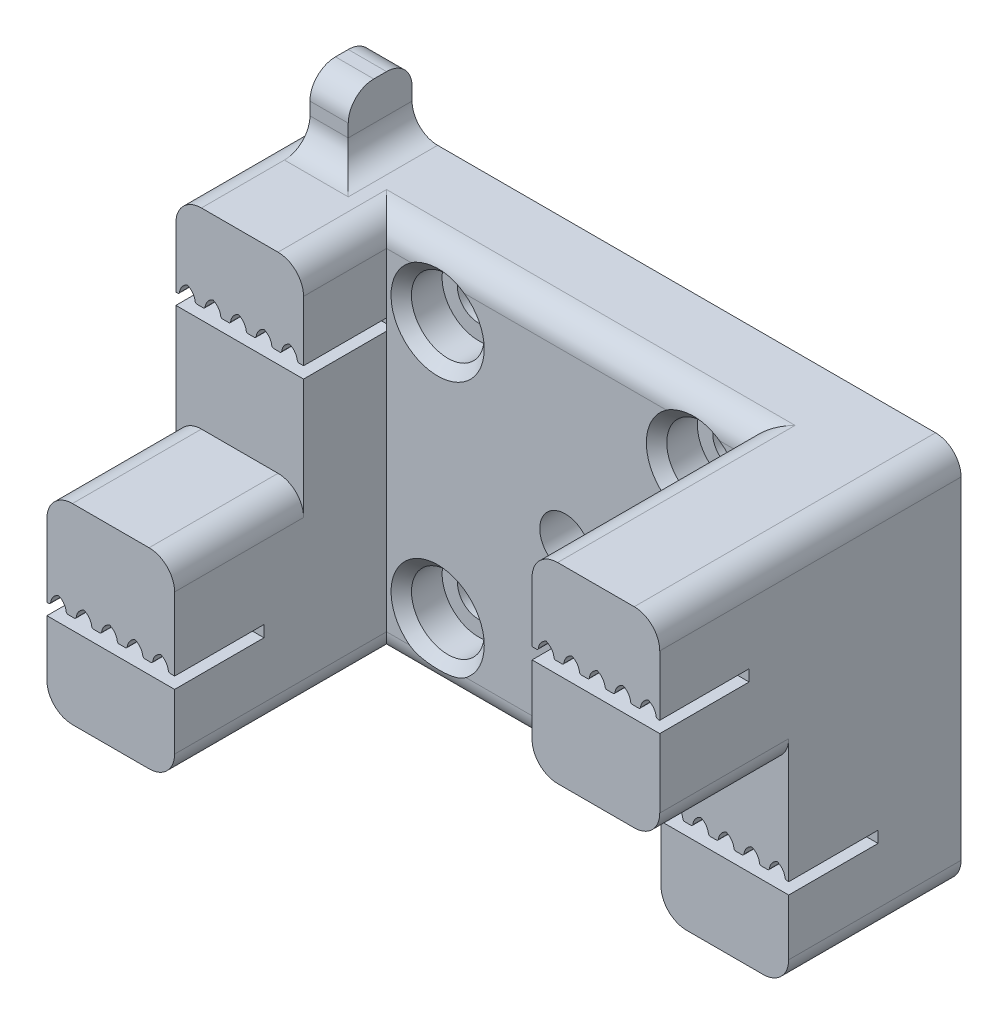
SolidWorks part; units mm, degrees
note: The reader was unsure of these and kept them because the rebuilt part matched: shared geometry of "Sketch2<3>".
ref_plane "Front Plane" through (0, 0, 0) normal (0, 0, 1) x (1, 0, 0)
ref_plane "Top Plane" through (0, 0, 0) normal (0, 1, 0) x (1, 0, 0)
ref_plane "Right Plane" through (0, 0, 0) normal (1, 0, 0) x (0, 0, -1)
sketch "Sketch1" plane through (0, 0, 0) normal (0, 0, 1) x (1, 0, 0)
  line L1 (-10, -10) -> (10, -10) construction
  line L2 (-10, -10) -> (-10, 10) construction
  line L3 (-10, 10) -> (10, 10) construction
  line L4 (10, -10) -> (10, 10) construction
  line L5 (-10, -10) -> (10, 10) construction
  line L6 (-10, 10) -> (10, -10) construction
  line L7 (-24, -15) -> (24, -15)
  line L8 (-24, -15) -> (-24, 15)
  line L9 (-24, 15) -> (24, 15)
  line L10 (24, -15) -> (24, 15)
  line L11 (-24, -15) -> (24, 15) construction
  line L12 (-24, 15) -> (24, -15) construction
  circle A0 centre (-10, 10) radius 1.65
  circle A1 centre (10, 10) radius 1.65
  circle A2 centre (10, -10) radius 1.65
  circle A3 centre (-9.9952, -10.0965) radius 1.65
  circle A4 centre (0, 0) radius 2
  point P0 (0, 0)
  dimension "D2" = 3.3
  dimension "D3" = 4
  dimension "D1" = 20
  dimension "D4" = 30
  dimension "D5" = 48
extrude "Boss-Extrude1" add sketch "Sketch1" along normal blind 7
sketch "Sketch2" plane through (0, 0, 7) normal (0, 0, 1) x (1, 0, 0)
  line L1 (-24, 15) -> (-14, 15)
  line L2 (-24, 15) -> (-24, -15)
  line L3 (-24, -15) -> (-14, -15)
  line L4 (-14, 15) -> (-14, -15)
  line L5 (-24, -15) -> (24, -15) construction
  line L7 (24, 15) -> (14, 15)
  line L8 (24, 15) -> (24, -15)
  line L9 (24, -15) -> (14, -15)
  line L10 (14, 15) -> (14, -15)
  line L11 (-14, -15) -> (-24, -15)
  line L12 (-14, -15) -> (-14, 0)
  line L13 (-14, 0) -> (-24, 0)
  line L14 (-24, -15) -> (-24, 0)
  line L15 (14, -15) -> (24, -15)
  line L16 (14, -15) -> (14, 0)
  line L17 (14, 0) -> (24, 0)
  line L18 (24, -15) -> (24, 0)
  line M1 (24, -15) -> (24, 15)
  line M2 (24, 15) -> (-24, 15)
  line M3 (-24, 15) -> (-24, -15)
  line M4 (-24, -15) -> (24, -15)
  dimension "D1" = 30
  dimension "D2" = 10
  dimension "D3" = 30
  dimension "D4" = 10
  dimension "D5" = 15
  dimension "D6" = 10
  dimension "D7" = 15
  dimension "D8" = 10
extrude "Boss-Extrude2" add sketch "Sketch2" along normal blind 16.6 contours L10 L17 L8 M2 | L4 L13 L2 M4
extrude "Boss-Extrude3" add sketch "Sketch2<3>" along normal blind 6.5 contours L17 L10 M4 M1 | L13 L4 M2 M3
sketch "Sketch2<3>" plane through (0, 0, 7) normal (0, 0, 1) x (1, 0, 0) same geometry as "Sketch2"
sketch "Sketch4" plane through (0, 0, 7) normal (0, 0, 1) x (1, 0, 0)
  circle A0 centre (-10, 10) radius 2.85
  circle A1 centre (10, 10) radius 2.85
  circle A2 centre (10, -10) radius 2.85
  circle A3 centre (-9.9952, -10.0965) radius 2.85
  dimension "D1" = 5.7
extrude "Cut-Extrude1" cut sketch "Sketch4" against normal blind 3.2
sketch "Sketch5" plane through (0, 0, 0) normal (0, 0, -1) x (-1, 0, 0)
  circle A0 centre (0, 0) radius 3.5
  dimension "D1" = 7
extrude "Cut-Extrude2" cut sketch "Sketch5" against normal blind 3
chamfer "Chamfer1" distance 0.8 angle 45 5 edges at (-3.5, 0, 0) (-7.15, 10, 7) (12.85, 10, 7) (-7.1452, -10.0965, 7) (12.85, -10, 7)
sketch "Sketch6" plane through (0, 0, 13.5) normal (0, 0, 1) x (1, 0, 0)
  line L7 (-16.343, 8.2928) -> (-15.8615, 8.2928)
  line L9 (-18.343, 8.2928) -> (-17.8615, 8.2928)
  line L10 (-20.343, 8.2928) -> (-19.8615, 8.2928)
  line L11 (-22.343, 8.2928) -> (-21.8615, 8.2928)
  line L12 (-23.8615, 8.2928) -> (-23.9973, 8.2928)
  line L14 (-23.9973, 8.2928) -> (-24, 8.2928)
  line L18 (-14.343, 8.2928) -> (-14, 8.2928)
  line L20 (-24.343, 8.2928) -> (-23.8615, 8.2928) [skipped]
  line L21 (-14.343, 8.2928) -> (-13.8615, 8.2928) [skipped]
  line L23 (-14, 6.5745) -> (-14, 8.2928)
  line L28 (-24, 8.2928) -> (-24, 7.3928)
  line L29 (-24, 7.3928) -> (-14, 7.3928)
  line L30 (-14, 8.2928) -> (-14, 7.3928)
  arc A13 (-17.1023, 9.2174) -> (-17.7128, 8.4232) centre (-16.7213, 8.2928) ccw
  arc A14 (-16.4917, 8.4232) -> (-17.1023, 9.2174) centre (-17.4832, 8.2928) ccw
  arc A15 (-16.4917, 8.4232) -> (-16.343, 8.2928) centre (-16.343, 8.4428) ccw
  arc A16 (-15.8615, 8.2928) -> (-15.7128, 8.4232) centre (-15.8615, 8.4428) ccw
  arc A19 (-19.1023, 9.2174) -> (-19.7128, 8.4232) centre (-18.7213, 8.2928) ccw
  arc A20 (-18.4917, 8.4232) -> (-19.1023, 9.2174) centre (-19.4832, 8.2928) ccw
  arc A21 (-18.4917, 8.4232) -> (-18.343, 8.2928) centre (-18.343, 8.4428) ccw
  arc A22 (-17.8615, 8.2928) -> (-17.7128, 8.4232) centre (-17.8615, 8.4428) ccw
  arc A23 (-21.1023, 9.2174) -> (-21.7128, 8.4232) centre (-20.7213, 8.2928) ccw
  arc A24 (-20.4917, 8.4232) -> (-21.1023, 9.2174) centre (-21.4832, 8.2928) ccw
  arc A25 (-20.4917, 8.4232) -> (-20.343, 8.2928) centre (-20.343, 8.4428) ccw
  arc A26 (-19.8615, 8.2928) -> (-19.7128, 8.4232) centre (-19.8615, 8.4428) ccw
  arc A27 (-23.1023, 9.2174) -> (-23.7128, 8.4232) centre (-22.7213, 8.2928) ccw
  arc A28 (-22.4917, 8.4232) -> (-23.1023, 9.2174) centre (-23.4832, 8.2928) ccw
  arc A29 (-22.4917, 8.4232) -> (-22.343, 8.2928) centre (-22.343, 8.4428) ccw
  arc A30 (-21.8615, 8.2928) -> (-21.7128, 8.4232) centre (-21.8615, 8.4428) ccw
  arc A34 (-23.8615, 8.2928) -> (-23.7128, 8.4232) centre (-23.8615, 8.4428) ccw
  arc A35 (-15.1023, 9.2174) -> (-15.7128, 8.4232) centre (-14.7213, 8.2928) ccw
  arc A36 (-14.4917, 8.4232) -> (-15.1023, 9.2174) centre (-15.4832, 8.2928) ccw
  arc A37 (-14.4917, 8.4232) -> (-14.343, 8.2928) centre (-14.343, 8.4428) ccw
  arc A39 (-24.4917, 8.4232) -> (-24.343, 8.2928) centre (-24.343, 8.4428) ccw [skipped]
  arc A40 (-24.4917, 8.4232) -> (-25.1023, 9.2174) centre (-25.4832, 8.2928) ccw [skipped]
  arc A41 (-25.1023, 9.2174) -> (-25.7128, 8.4232) centre (-24.7213, 8.2928) ccw [skipped]
  arc A42 (-13.8615, 8.2928) -> (-13.7128, 8.4232) centre (-13.8615, 8.4428) ccw [skipped]
  dimension "D2" = 2
  dimension "D3" = 10
  dimension "D4" = 0.9
  dimension "D1" = 5
extrude "Cut-Extrude3" cut sketch "Sketch6" against normal blind 7 and the other way blind 100 contours L18 A37 A36 A35 A16 L7 A15 A14 A13 A22 L9 A21 A20 A19 A26 L10 A25 A24 A23 A30 L11 A29 A28 A27 A34 L12 L14 L28 L29 L30
mirror "Mirror3" about plane through (0, 0, 0) normal (1, 0, 0) of "Cut-Extrude3"
pattern_linear "LPattern1" count 2 spacing 16 along (0, -1, 0) of "Mirror3", "Cut-Extrude3"
sketch "Sketch7" plane through (0, 0, 6.5) normal (0, 0, 1) x (1, 0, 0)
  line L0 (-14, 15) -> (-14, 8.2928) construction
  line L1 (-24, -8.6072) -> (-14, -8.6072)
  line L2 (-24, -8.6072) -> (-24, -6.1072)
  line L3 (-24, -6.1072) -> (-14, -6.1072)
  line L4 (-14, -8.6072) -> (-14, -6.1072)
  line L6 (14, 7.3928) -> (24, 7.3928)
  line L7 (14, 7.3928) -> (14, 9.8928)
  line L8 (14, 9.8928) -> (24, 9.8928)
  line L9 (24, 7.3928) -> (24, 9.8928)
  line L14 (14, 8.2928) -> (14, 7.3928)
  line L15 (14, 7.3928) -> (24, 7.3928)
  line L16 (24, 7.3928) -> (24, 8.2928)
  line L17 (24, 8.2928) -> (23.8615, 8.2928)
  line L18 (22.343, 8.2928) -> (21.8615, 8.2928)
  line L19 (20.343, 8.2928) -> (19.8615, 8.2928)
  line L20 (18.343, 8.2928) -> (17.8615, 8.2928)
  line L21 (16.343, 8.2928) -> (15.8615, 8.2928)
  line L22 (14.343, 8.2928) -> (14, 8.2928)
  line L24 (14, 7.3928) -> (24, 7.3928)
  line L25 (24, 7.3928) -> (24, 8.2928)
  line L26 (24, 8.2928) -> (23.8615, 8.2928)
  line L27 (22.343, 8.2928) -> (21.8615, 8.2928)
  line L28 (20.343, 8.2928) -> (19.8615, 8.2928)
  line L29 (18.343, 8.2928) -> (17.8615, 8.2928)
  line L30 (16.343, 8.2928) -> (15.8615, 8.2928)
  line L31 (14.343, 8.2928) -> (14, 8.2928)
  line L32 (23.8615, 8.2928) -> (24, 8.2928)
  line L33 (24, 8.2928) -> (24, 15)
  line L34 (24, 15) -> (14, 15)
  line L35 (14, 15) -> (14, 8.2928)
  line L36 (14, 8.2928) -> (14.343, 8.2928)
  line L37 (15.8615, 8.2928) -> (16.343, 8.2928)
  line L38 (17.8615, 8.2928) -> (18.343, 8.2928)
  line L39 (19.8615, 8.2928) -> (20.343, 8.2928)
  line L40 (21.8615, 8.2928) -> (22.343, 8.2928)
  line L41 (23.8615, 8.2928) -> (24, 8.2928)
  line L42 (24, 8.2928) -> (24, 15)
  line L43 (24, 15) -> (14, 15)
  line L44 (14, 15) -> (14, 8.2928)
  line L45 (14, 8.2928) -> (14.343, 8.2928)
  line L46 (15.8615, 8.2928) -> (16.343, 8.2928)
  line L47 (17.8615, 8.2928) -> (18.343, 8.2928)
  line L48 (19.8615, 8.2928) -> (20.343, 8.2928)
  line L49 (21.8615, 8.2928) -> (22.343, 8.2928)
  line L54 (14, 8.2928) -> (14, 7.3928)
  arc A21 (23.7128, 8.4232) -> (23.8615, 8.2928) centre (23.8615, 8.4428) ccw
  arc A22 (23.7128, 8.4232) -> (23.1023, 9.2174) centre (22.7213, 8.2928) ccw
  arc A23 (23.1023, 9.2174) -> (22.4917, 8.4232) centre (23.4832, 8.2928) ccw
  arc A24 (22.343, 8.2928) -> (22.4917, 8.4232) centre (22.343, 8.4428) ccw
  arc A25 (21.7128, 8.4232) -> (21.8615, 8.2928) centre (21.8615, 8.4428) ccw
  arc A26 (21.7128, 8.4232) -> (21.1023, 9.2174) centre (20.7213, 8.2928) ccw
  arc A27 (21.1023, 9.2174) -> (20.4917, 8.4232) centre (21.4832, 8.2928) ccw
  arc A28 (20.343, 8.2928) -> (20.4917, 8.4232) centre (20.343, 8.4428) ccw
  arc A29 (19.7128, 8.4232) -> (19.8615, 8.2928) centre (19.8615, 8.4428) ccw
  arc A30 (19.7128, 8.4232) -> (19.1023, 9.2174) centre (18.7213, 8.2928) ccw
  arc A31 (19.1023, 9.2174) -> (18.4917, 8.4232) centre (19.4832, 8.2928) ccw
  arc A32 (18.343, 8.2928) -> (18.4917, 8.4232) centre (18.343, 8.4428) ccw
  arc A33 (17.7128, 8.4232) -> (17.8615, 8.2928) centre (17.8615, 8.4428) ccw
  arc A34 (17.7128, 8.4232) -> (17.1023, 9.2174) centre (16.7213, 8.2928) ccw
  arc A35 (17.1023, 9.2174) -> (16.4917, 8.4232) centre (17.4832, 8.2928) ccw
  arc A36 (16.343, 8.2928) -> (16.4917, 8.4232) centre (16.343, 8.4428) ccw
  arc A37 (15.7128, 8.4232) -> (15.8615, 8.2928) centre (15.8615, 8.4428) ccw
  arc A38 (15.7128, 8.4232) -> (15.1023, 9.2174) centre (14.7213, 8.2928) ccw
  arc A39 (15.1023, 9.2174) -> (14.4917, 8.4232) centre (15.4832, 8.2928) ccw
  arc A40 (14.343, 8.2928) -> (14.4917, 8.4232) centre (14.343, 8.4428) ccw
  arc A41 (23.7128, 8.4232) -> (23.8615, 8.2928) centre (23.8615, 8.4428) ccw
  arc A42 (23.7128, 8.4232) -> (23.1023, 9.2174) centre (22.7213, 8.2928) ccw
  arc A43 (23.1023, 9.2174) -> (22.4917, 8.4232) centre (23.4832, 8.2928) ccw
  arc A44 (22.343, 8.2928) -> (22.4917, 8.4232) centre (22.343, 8.4428) ccw
  arc A45 (21.7128, 8.4232) -> (21.8615, 8.2928) centre (21.8615, 8.4428) ccw
  arc A46 (21.7128, 8.4232) -> (21.1023, 9.2174) centre (20.7213, 8.2928) ccw
  arc A47 (21.1023, 9.2174) -> (20.4917, 8.4232) centre (21.4832, 8.2928) ccw
  arc A48 (20.343, 8.2928) -> (20.4917, 8.4232) centre (20.343, 8.4428) ccw
  arc A49 (19.7128, 8.4232) -> (19.8615, 8.2928) centre (19.8615, 8.4428) ccw
  arc A50 (19.7128, 8.4232) -> (19.1023, 9.2174) centre (18.7213, 8.2928) ccw
  arc A51 (19.1023, 9.2174) -> (18.4917, 8.4232) centre (19.4832, 8.2928) ccw
  arc A52 (18.343, 8.2928) -> (18.4917, 8.4232) centre (18.343, 8.4428) ccw
  arc A53 (17.7128, 8.4232) -> (17.8615, 8.2928) centre (17.8615, 8.4428) ccw
  arc A54 (17.7128, 8.4232) -> (17.1023, 9.2174) centre (16.7213, 8.2928) ccw
  arc A55 (17.1023, 9.2174) -> (16.4917, 8.4232) centre (17.4832, 8.2928) ccw
  arc A56 (16.343, 8.2928) -> (16.4917, 8.4232) centre (16.343, 8.4428) ccw
  arc A57 (15.7128, 8.4232) -> (15.8615, 8.2928) centre (15.8615, 8.4428) ccw
  arc A58 (15.7128, 8.4232) -> (15.1023, 9.2174) centre (14.7213, 8.2928) ccw
  arc A59 (15.1023, 9.2174) -> (14.4917, 8.4232) centre (15.4832, 8.2928) ccw
  arc A60 (14.343, 8.2928) -> (14.4917, 8.4232) centre (14.343, 8.4428) ccw
  arc A61 (14.343, 8.2928) -> (14.4917, 8.4232) centre (14.343, 8.4428) ccw
  arc A62 (15.1023, 9.2174) -> (14.4917, 8.4232) centre (15.4832, 8.2928) ccw
  arc A63 (15.7128, 8.4232) -> (15.1023, 9.2174) centre (14.7213, 8.2928) ccw
  arc A64 (15.7128, 8.4232) -> (15.8615, 8.2928) centre (15.8615, 8.4428) ccw
  arc A65 (16.343, 8.2928) -> (16.4917, 8.4232) centre (16.343, 8.4428) ccw
  arc A66 (17.1023, 9.2174) -> (16.4917, 8.4232) centre (17.4832, 8.2928) ccw
  arc A67 (17.7128, 8.4232) -> (17.1023, 9.2174) centre (16.7213, 8.2928) ccw
  arc A68 (17.7128, 8.4232) -> (17.8615, 8.2928) centre (17.8615, 8.4428) ccw
  arc A69 (18.343, 8.2928) -> (18.4917, 8.4232) centre (18.343, 8.4428) ccw
  arc A70 (19.1023, 9.2174) -> (18.4917, 8.4232) centre (19.4832, 8.2928) ccw
  arc A71 (19.7128, 8.4232) -> (19.1023, 9.2174) centre (18.7213, 8.2928) ccw
  arc A72 (19.7128, 8.4232) -> (19.8615, 8.2928) centre (19.8615, 8.4428) ccw
  arc A73 (20.343, 8.2928) -> (20.4917, 8.4232) centre (20.343, 8.4428) ccw
  arc A74 (21.1023, 9.2174) -> (20.4917, 8.4232) centre (21.4832, 8.2928) ccw
  arc A75 (21.7128, 8.4232) -> (21.1023, 9.2174) centre (20.7213, 8.2928) ccw
  arc A76 (21.7128, 8.4232) -> (21.8615, 8.2928) centre (21.8615, 8.4428) ccw
  arc A77 (22.343, 8.2928) -> (22.4917, 8.4232) centre (22.343, 8.4428) ccw
  arc A78 (23.1023, 9.2174) -> (22.4917, 8.4232) centre (23.4832, 8.2928) ccw
  arc A79 (23.7128, 8.4232) -> (23.1023, 9.2174) centre (22.7213, 8.2928) ccw
  arc A80 (23.7128, 8.4232) -> (23.8615, 8.2928) centre (23.8615, 8.4428) ccw
  arc A81 (14.343, 8.2928) -> (14.4917, 8.4232) centre (14.343, 8.4428) ccw
  arc A82 (15.1023, 9.2174) -> (14.4917, 8.4232) centre (15.4832, 8.2928) ccw
  arc A83 (15.7128, 8.4232) -> (15.1023, 9.2174) centre (14.7213, 8.2928) ccw
  arc A84 (15.7128, 8.4232) -> (15.8615, 8.2928) centre (15.8615, 8.4428) ccw
  arc A85 (16.343, 8.2928) -> (16.4917, 8.4232) centre (16.343, 8.4428) ccw
  arc A86 (17.1023, 9.2174) -> (16.4917, 8.4232) centre (17.4832, 8.2928) ccw
  arc A87 (17.7128, 8.4232) -> (17.1023, 9.2174) centre (16.7213, 8.2928) ccw
  arc A88 (17.7128, 8.4232) -> (17.8615, 8.2928) centre (17.8615, 8.4428) ccw
  arc A89 (18.343, 8.2928) -> (18.4917, 8.4232) centre (18.343, 8.4428) ccw
  arc A90 (19.1023, 9.2174) -> (18.4917, 8.4232) centre (19.4832, 8.2928) ccw
  arc A91 (19.7128, 8.4232) -> (19.1023, 9.2174) centre (18.7213, 8.2928) ccw
  arc A92 (19.7128, 8.4232) -> (19.8615, 8.2928) centre (19.8615, 8.4428) ccw
  arc A93 (20.343, 8.2928) -> (20.4917, 8.4232) centre (20.343, 8.4428) ccw
  arc A94 (21.1023, 9.2174) -> (20.4917, 8.4232) centre (21.4832, 8.2928) ccw
  arc A95 (21.7128, 8.4232) -> (21.1023, 9.2174) centre (20.7213, 8.2928) ccw
  arc A96 (21.7128, 8.4232) -> (21.8615, 8.2928) centre (21.8615, 8.4428) ccw
  arc A97 (22.343, 8.2928) -> (22.4917, 8.4232) centre (22.343, 8.4428) ccw
  arc A98 (23.1023, 9.2174) -> (22.4917, 8.4232) centre (23.4832, 8.2928) ccw
  arc A99 (23.7128, 8.4232) -> (23.1023, 9.2174) centre (22.7213, 8.2928) ccw
  arc A100 (23.7128, 8.4232) -> (23.8615, 8.2928) centre (23.8615, 8.4428) ccw
  dimension "D1" = 2.5
  dimension "D2" = 0
  dimension "D3" = 0
  dimension "D4" = 2.5
  dimension "D5" = 10
extrude "Boss-Extrude4" add sketch "Sketch7" along normal blind 10.1
fillet "Fillet1" radius 2 14 edges at (0, 15, 7) (0, -15, 7) (14, 15, 15.3) (14, 0, 18.55) (24, 0, 18.55) (-14, -15, 15.3) (-14, 0, 18.55) (-24, 0, 18.55) (14, -15, 10.25) (-14, 15, 10.25) (24, -15, 6.75) (-24, -15, 11.8) (-24, 15, 6.75) (24, 15, 11.8)
sketch "Sketch10" plane through (0, 15, 0) normal (0, 1, 0) x (1, 0, 0)
  line L0 (22, 0) -> (-22, 0) construction
  line L1 (-22, 0) -> (-19, 0)
  line L2 (-22, 0) -> (-22, -5)
  line L3 (-22, -5) -> (-19, -5)
  line L4 (-19, 0) -> (-19, -5)
  line L5 (-16, -5) -> (16, -5) construction
  dimension "D1" = 3
  dimension "D2" = 19
extrude "Boss-Extrude7" add sketch "Sketch10" along normal blind 5
fillet "Fillet3" radius 2 4 edges at (-20.5, 15, 5) (-20.5, 20, 0) (-20.5, 20, 5) (-19, 15, 2.5)
